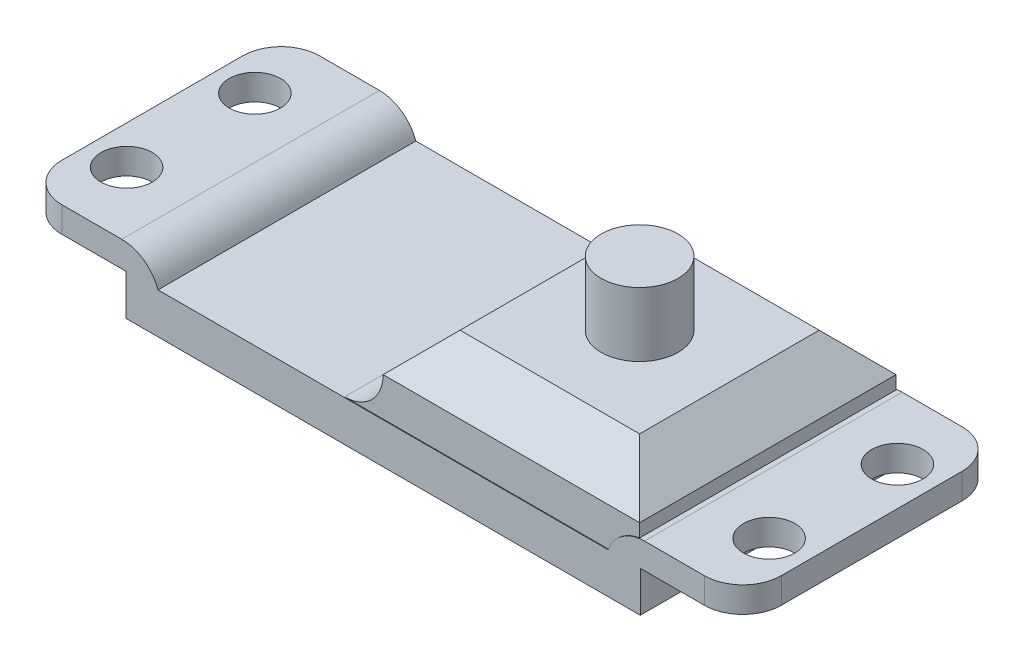
SolidWorks part; units mm, degrees
ref_plane "Front Plane" through (0, 0, 0) normal (0, 0, 1) x (1, 0, 0)
ref_plane "Top Plane" through (0, 0, 0) normal (0, 1, 0) x (1, 0, 0)
ref_plane "Right Plane" through (0, 0, 0) normal (1, 0, 0) x (0, 0, -1)
sketch "Sketch1" plane through (0, 0, 0) normal (0, 1, 0) x (1, 0, 0)
  line L1 (-20.05, -10.05) -> (20.05, -10.05)
  line L2 (-20.05, -10.05) -> (-20.05, 10.05)
  line L3 (-20.05, 10.05) -> (20.05, 10.05)
  line L4 (20.05, -10.05) -> (20.05, 10.05)
  line L5 (-20.05, -10.05) -> (20.05, 10.05) construction
  line L6 (-20.05, 10.05) -> (20.05, -10.05) construction
  point P0 (0, 0)
  dimension "D1" = 40.1
  dimension "D2" = 20.1
extrude "Boss-Extrude1" add sketch "Sketch1" along normal blind 3.175
sketch "Sketch2" plane through (0, 3.175, 0) normal (0, 1, 0) x (1, 0, 0)
  line L0 (-20.05, -10.05) -> (20.05, -10.05) construction
  line L1 (20.05, 10.05) -> (17.55, 10.05)
  line L2 (20.05, 10.05) -> (20.05, -10.05)
  line L3 (20.05, -10.05) -> (17.55, -10.05)
  line L4 (17.55, 10.05) -> (17.55, -10.05)
  dimension "D1" = 2.5
extrude "Boss-Extrude2" add sketch "Sketch2" along normal blind 2
sketch "Sketch3" plane through (20.05, 0, 0) normal (1, 0, 0) x (0, 0, -1)
  line L0 (10.05, 5.175) -> (10.05, 0) construction
  line L1 (-10.05, 5.175) -> (10.05, 5.175)
  line L2 (-10.05, 5.175) -> (-10.05, 3.175)
  line L3 (-10.05, 3.175) -> (10.05, 3.175)
  line L4 (10.05, 5.175) -> (10.05, 3.175)
  line L5 (10.05, 5.175) -> (10.05, 3.175) construction
extrude "Boss-Extrude3" add sketch "Sketch3" along normal blind 8
sketch "Sketch4" plane through (0, 3.175, 0) normal (0, -1, 0) x (1, 0, 0)
  line L0 (25.05, 5) -> (25.05, -5) construction
  line L1 (1.7463, 0) -> (-1.7463, 0) construction
  line L2 (20.05, 10.05) -> (20.05, -10.05) construction
  circle A0 centre (25.05, 5) radius 2
  circle A1 centre (25.05, -5) radius 2
  point P4 (25.05, 0)
  dimension "D1" = 4
  dimension "D2" = 10
  dimension "D3" = 5
extrude "Cut-Extrude1" cut sketch "Sketch4" against normal through all both and the other way through all
fillet "Fillet1" radius 3 1 edges at (17.55, 5.175, 0)
fillet "Fillet2" radius 3 2 edges at (28.05, 4.175, -10.05) (28.05, 4.175, 10.05)
mirror "Mirror2" about plane through (0, 0, 0) normal (1, 0, 0) of "Fillet2", "Fillet1", "Cut-Extrude1", "Boss-Extrude3", "Boss-Extrude2"
sketch "Sketch7" plane through (0, 3.175, 0) normal (0, 1, 0) x (1, 0, 0)
  line L1 (-0.05, 10) -> (19.95, 10)
  line L2 (-0.05, 10) -> (-0.05, -10)
  line L3 (-0.05, -10) -> (19.95, -10)
  line L4 (19.95, 10) -> (19.95, -10)
  line L5 (-0.05, 10) -> (19.95, -10) construction
  line L6 (-0.05, -10) -> (19.95, 10) construction
  circle A0 centre (25.05, -5) radius 2 construction
  point P0 (9.95, 0)
  point P7 (0, 0)
  dimension "D1" = 15.1
  dimension "D2" = 20
  dimension "D3" = 20
extrude "Boss-Extrude5" add sketch "Sketch7" along normal blind 6
sketch "Sketch5" plane through (0, 9.175, 0) normal (0, 1, 0) x (1, 0, 0)
  circle A0 centre (9.95, 0) radius 3
  circle A1 centre (25.05, -5) radius 2 construction
  dimension "D1" = 6
  dimension "D2" = 15.1
extrude "Boss-Extrude4" add sketch "Sketch5" along normal blind 5
fillet "Fillet4" radius 3 1 edges at (-0.05, 3.175, 0)
chamfer "Chamfer1" distance 3 angle 45 4 edges at (19.95, 9.175, 0) (9.95, 9.175, -10) (-0.05, 9.175, 0) (9.95, 9.175, 10)
